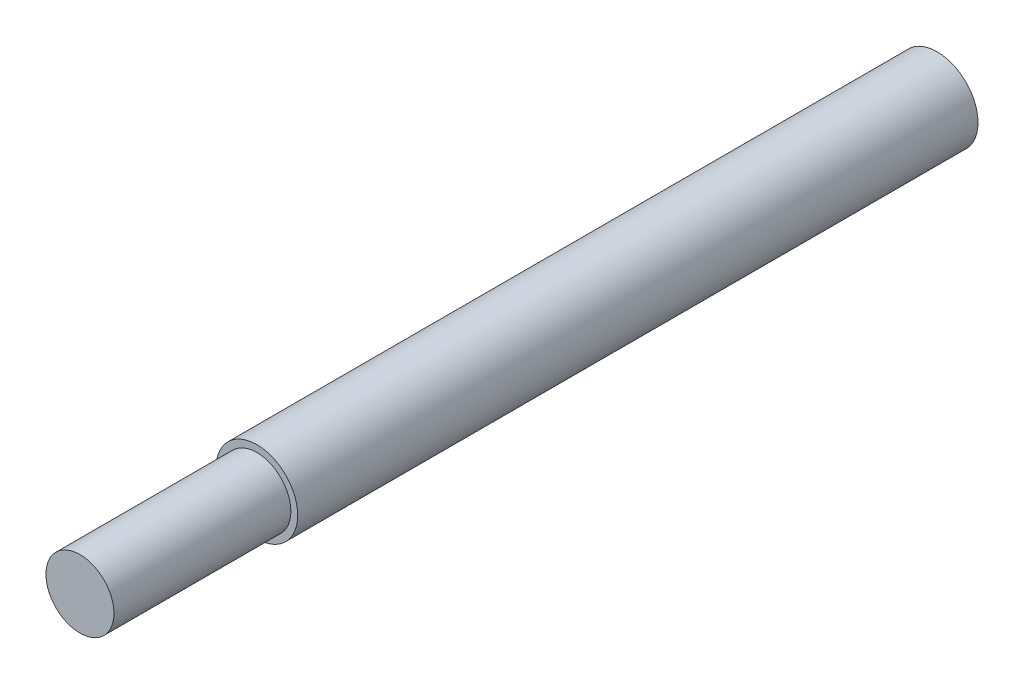
SolidWorks part; units mm, degrees
ref_plane "前视基准面" through (0, 0, 0) normal (0, 0, 1) x (1, 0, 0)
ref_plane "上视基准面" through (0, 0, 0) normal (0, 1, 0) x (1, 0, 0)
ref_plane "右视基准面" through (0, 0, 0) normal (1, 0, 0) x (0, 0, -1)
sketch "草图1" plane through (0, 0, 0) normal (0, 0, 1) x (1, 0, 0)
  circle A0 centre (0, 0) radius 3.37
extrude "凸台-拉伸1" add sketch "草图1" along normal mid plane 50 from surface starting at plane "前视基准面"
sketch "草图3" plane through (0, 0, 25) normal (0, 0, 1) x (1, 0, 0)
  circle A1 centre (0, 0) radius 3.37
  circle A2 centre (0, 0) radius 3.37
  dimension "D1" = 0
extrude "凸台-拉伸3" add sketch "草图3" along normal blind 13
sketch "草图4" plane through (0, 0, 38) normal (0, 0, 1) x (1, 0, 0)
  circle A0 centre (0, 0) radius 2.5
  circle A1 centre (0, 0) radius 3.37
  dimension "D1" = 5
extrude "切除-拉伸1" cut sketch "草图4" against normal blind 13
sketch "草图5" plane through (0, 0, 25) normal (0, 0, 1) x (1, 0, 0)
  circle A0 centre (0, 0) radius 3.37
  circle A2 centre (0, 0) radius 3
  dimension "D1" = 6
extrude "切除-拉伸2" cut sketch "草图5" against normal blind 14.3
sketch "草图6" plane through (0, 0, -25) normal (0, 0, -1) x (-1, 0, 0)
  circle A0 centre (0, 0) radius 3.37
  circle A1 centre (0, 0) radius 3
  dimension "D1" = 6
extrude "切除-拉伸3" cut sketch "草图6" against normal blind 14.3
sketch "草图8" plane through (0, 0, 10.7) normal (0, 0, 1) x (1, 0, 0)
  circle A0 centre (0, 0) radius 3
  circle A1 centre (0, 0) radius 3.37
  circle A2 centre (0, 0) radius 3.37
  dimension "D1" = 0
extrude "切除-拉伸5" cut sketch "草图8" against normal through all both and the other way through all
